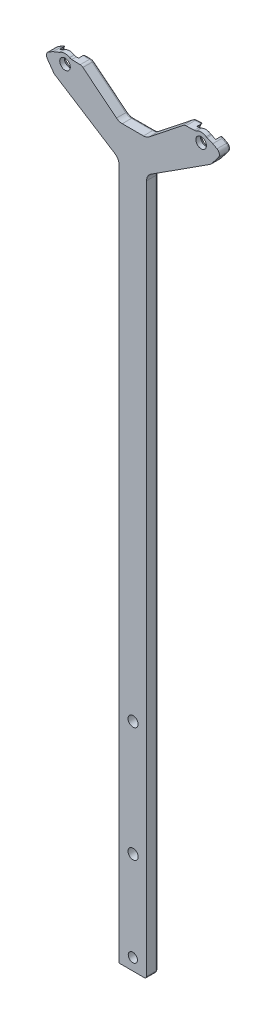
SolidWorks part; units mm, degrees
ref_plane "Płaszczyzna przednia" through (0, 0, 0) normal (0, 0, 1) x (1, 0, 0)
ref_plane "Płaszczyzna górna" through (0, 0, 0) normal (0, 1, 0) x (1, 0, 0)
ref_plane "Płaszczyzna prawa" through (0, 0, 0) normal (1, 0, 0) x (0, 0, -1)
sketch "Szkic1" plane through (0, 0, 158.2318) normal (0, 0, -1) x (-1, 0, 0)
  line L1 (11.9733, -23.8324) -> (17.9733, -23.8324)
  line L2 (11.9733, -23.8324) -> (11.9733, 126.5141)
  line L4 (17.9733, -23.8324) -> (17.9733, 126.5079)
  line L8 (12.6702, 134.6055) -> (17.2697, 134.6055)
  line L17 (3.4265, 141.1371) -> (1.5863, 141.2045)
  line L18 (26.424, 141.1367) -> (28.2508, 141.2)
  line L19 (-2.4001, 140.6758) -> (-1.1701, 141.1719)
  line L21 (32.3012, 140.6529) -> (31.0255, 141.1663)
  line L24 (25.8325, 140.917) -> (18.522, 135.0461)
  line L25 (4.0114, 140.9212) -> (11.4273, 135.0386)
  line L27 (-1.8525, 136.5015) -> (11.0555, 128.196)
  line L29 (31.9245, 136.4876) -> (18.8992, 128.195)
  line L30 (-2.4001, 140.6758) -> (-3.3279, 140.1722)
  line L31 (-3.6355, 138.6735) -> (-2.1257, 136.7621)
  line L32 (32.3012, 140.6529) -> (33.2355, 140.1438)
  line L33 (33.5729, 138.6876) -> (32.2285, 136.7901)
  circle A0 centre (14.9235, 23.2256) radius 1.1 construction
  circle A1 centre (14.9235, -1.7745) radius 1.1 construction
  circle A2 centre (14.9733, -21.2743) radius 1 construction
  circle A3 centre (14.9235, 23.2256) radius 1.1
  circle A4 centre (14.9235, -1.7745) radius 1.1
  circle A5 centre (14.9733, -21.2743) radius 1
  circle A6 centre (0.1233, 139.6055) radius 1.15 construction
  circle A7 centre (29.7233, 139.6055) radius 1.15 construction
  circle A8 centre (0.1233, 139.6055) radius 1.15
  circle A9 centre (29.7233, 139.6055) radius 1.15
  arc A12 (1.1231, 141.3377) -> (-0.9884, 141.2681) centre (0.1233, 139.6055) ccw
  arc A13 (30.8404, 141.2645) -> (28.7185, 141.3348) centre (29.7233, 139.6055) ccw
  arc A14 (-2.1257, 136.7621) -> (-1.8525, 136.5015) centre (-1.3114, 137.3424) ccw
  arc A15 (3.4265, 141.1371) -> (4.0114, 140.9212) centre (3.3899, 140.1378) cw
  arc A16 (1.1231, 141.3377) -> (1.5863, 141.2045) centre (1.6229, 142.2038) ccw
  arc A17 (-1.1701, 141.1719) -> (-0.9884, 141.2681) centre (-1.5442, 142.0993) ccw
  arc A18 (-2.6, 140.5673) -> (-2.4001, 140.6758) centre (-2.026, 139.7484) cw
  arc A19 (31.9245, 136.4876) -> (32.2285, 136.7901) centre (31.3875, 137.3312) ccw
  arc A20 (31.0255, 141.1663) -> (30.8404, 141.2645) centre (31.3989, 142.094) cw
  arc A21 (28.2508, 141.2) -> (28.7185, 141.3348) centre (28.2161, 142.1994) ccw
  arc A22 (25.8325, 140.917) -> (26.424, 141.1367) centre (26.4587, 140.1373) cw
  arc A23 (32.505, 140.5418) -> (32.3012, 140.6529) centre (31.9279, 139.7252) ccw
  arc A24 (17.2697, 134.6055) -> (18.522, 135.0461) centre (17.2697, 136.6055) ccw
  arc A25 (12.6702, 134.6055) -> (11.4273, 135.0386) centre (12.6702, 136.6055) cw
  arc A26 (11.9733, 126.5141) -> (11.0555, 128.196) centre (9.9733, 126.5141) ccw
  arc A27 (17.9733, 126.5079) -> (18.8992, 128.195) centre (19.9733, 126.5079) cw
  arc A28 (33.5729, 138.6876) -> (33.2355, 140.1438) centre (32.757, 139.2657) ccw
  arc A29 (-3.6355, 138.6735) -> (-3.3279, 140.1722) centre (-2.8508, 139.2933) cw
  point P20 (-1.0142, 136.6055)
  point P35 (1.3112, 141.2146)
  point P40 (-1.0645, 141.2146)
  point P46 (31.1097, 136.6055)
  point P49 (30.9178, 141.2097)
  point P52 (28.5289, 141.2097)
  point P59 (17.9733, 134.6055)
  point P62 (11.9733, 134.6055)
  point P65 (11.9733, 127.6055)
  point P68 (17.9733, 127.6055)
  point P69 (0, 0)
  point P74 (34.2233, 139.6055)
  point P77 (-4.3717, 139.6055)
  dimension "D5" = 2
  dimension "D11" = 1
  dimension "D1" = 3
  dimension "D2" = 3
  dimension "D3" = 5
  dimension "D6" = 12
  dimension "D7" = 9
  dimension "D8" = 9
  dimension "D9" = 4.5
  dimension "D10" = 4.4951
extrude "Dodanie-wyciągnięcie3" add sketch "Szkic1" along normal blind 2.5 contours A29 L31 A14 L27 A26 L2 L1 L4 A27 L29 A19 L33 A28 L32 L21 A20 A13 A21 L18 A22 L24 A24 L8 A25 L25 A15 L17 A16 A12 A17 L19 L30 A9 A8 A5 A4 A3 region at (-14.9831, 70.1288, 158.2318)
sketch "Szkic4" plane through (0, 0, 155.7318) normal (0, 0, -1) x (-1, 0, 0)
  circle A0 centre (0.1233, 139.6055) radius 2.5
  circle A1 centre (29.7233, 139.6055) radius 2.5
  dimension "D1" = 5
  dimension "D2" = 5
extrude "Wytnij-wyciągnięcie2" cut sketch "Szkic4" against normal blind 1.5
fillet "Zaokrąglenie3" radius 0.5 22 edges at (-27.1043, 141.1603, 155.7318) (-26.1105, 141.0747, 155.7318) (-2.743, 141.1622, 155.7318) (-3.7362, 141.0759, 155.7318) (-7.7193, 137.9799, 155.7318) (-12.0121, 134.7169, 155.7318) (-14.9699, 134.6055, 155.7318) (-17.9334, 134.7189, 155.7318) (2.8806, 137.7178, 155.7318) (3.8304, 139.4944, 155.7318) (-32.7683, 140.3983, 155.7318) (-33.7312, 139.4915, 155.7318) (-32.0929, 136.6224, 155.7318) (-17.9733, 51.3378, 155.7318) (-18.22, 127.4701, 155.7318) (-14.9733, -23.8324, 155.7318) (-22.1772, 137.9815, 155.7318) (2.864, 140.424, 155.7318) (-0.3509, 137.1159, 155.7318) (-29.497, 137.1158, 155.7318) (-32.9007, 137.7388, 155.7318) (-25.4119, 132.3413, 155.7318)
fillet "Zaokrąglenie4" radius 0.5 6 edges at (2.2639, 137.0379, 155.7318) (-11.9733, -23.8324, 157.2318) (-11.9733, -23.6859, 155.8783) (-11.9733, 51.5909, 155.7318) (-11.7289, 127.4721, 155.7318) (-4.6015, 132.3488, 155.7318)
sketch "Szkic6" plane through (0, 0, 155.7318) normal (0, 0, -1) x (-1, 0, 0)
  line L0 (12.6702, 134.6055) -> (17.2697, 134.6055) construction
  line L1 (15.085, 128.6055) -> (15.085, 132.6055) construction
  line L2 (15.085, 128.6055) -> (15.085, 132.6055)
  arc A0 (15.085, 132.6055) -> (15.085, 128.6055) centre (15.085, 130.6055) ccw
  dimension "D1" = 4
  dimension "D2" = 4
revolve "Obrót7" add sketch "Szkic6" angle 180 about L1
